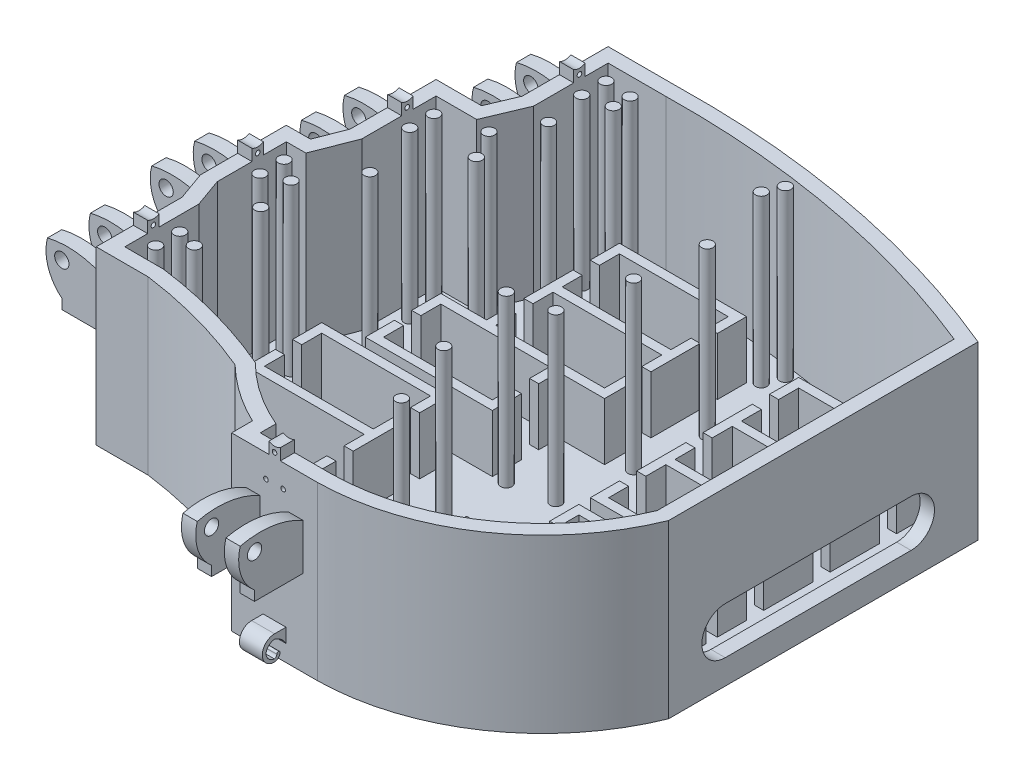
SolidWorks part; units mm, degrees
ref_plane "Front Plane" through (0, 0, 0) normal (0, 0, 1) x (1, 0, 0)
ref_plane "Top Plane" through (0, 0, 0) normal (0, 1, 0) x (1, 0, 0)
ref_plane "Right Plane" through (0, 0, 0) normal (1, 0, 0) x (0, 0, -1)
ref_plane "Palm Side Plane" through (0, 38.1, 0) normal (0, 1, 0) x (1, 0, 0)
ref_plane "Left Side Plane" through (0, 0, 63.5) normal (0, 0, 1) x (1, 0, 0)
ref_plane "Top Side Plane" through (-69.85, 0, 0) normal (1, 0, 0) x (0, 0, -1)
ref_plane "Wrist Plane" through (62.9138, 0, 0) normal (1, 0, 0) x (0, 0, -1)
sketch "Hand Direction Arrow" plane through (0, 38.1, 0) normal (0, 1, 0) x (1, 0, 0)
  line L0 (49.8191, -114.0829) -> (-36.738, -114.0829) construction
  line L1 (-36.738, -114.0829) -> (-22.4792, -131.555) construction
  line L2 (-36.738, -114.0829) -> (-22.4792, -99.8241) construction
sketch "Sketch2" plane through (0, 0, 0) normal (0, 1, 0) x (1, 0, 0)
  line L5 (-69.85, -63.5) -> (69.85, 63.5) construction
  line L6 (-69.85, 63.5) -> (69.85, -63.5) construction
  line L7 (-20.7784, 52.7587) -> (-36.189, 52.7587)
  line L8 (-36.189, 52.7587) -> (-36.189, 33.7087)
  line L9 (-42.9594, -42.4913) -> (-54.5039, -42.4913)
  line L10 (-54.5039, -42.4913) -> (-54.5039, -23.4413)
  line L11 (-54.5039, -23.4413) -> (-56.7676, -17.0913)
  line L12 (-51.4171, 1.9587) -> (-48.9477, 8.3087)
  line L14 (-56.7676, -17.0913) -> (-56.7676, 1.9587)
  line L15 (-56.7676, 1.9587) -> (-51.4171, 1.9587)
  line L16 (-38.8642, 27.3587) -> (-36.189, 33.7087)
  line L19 (15.3118, -63.2103) -> (-3.7382, -63.2103)
  line L20 (-3.7382, -63.2103) -> (-3.7382, -58.593)
  line L21 (61.5724, -31.5884) -> (61.5724, 37.0553)
  line L22 (-48.9477, 8.3087) -> (-48.9477, 27.3587)
  line L23 (-48.9477, 27.3587) -> (-38.8642, 27.3587)
  arc A0 (61.5724, 37.0553) -> (-20.7784, 52.7587) centre (-16.6219, -149.2259) ccw
  arc A2 (-42.9594, -42.4913) -> (-16.4221, -49.7553) centre (-56.8306, -145.2734) cw
  arc A5 (-3.7382, -58.593) -> (-16.4221, -49.7553) centre (16.7508, -15.6666) cw
  arc A6 (15.3118, -63.2103) -> (61.5724, -31.5884) centre (14.5642, -12.4678) ccw
  point P0 (0, 0)
  dimension "D1" = 19.05
  dimension "D2" = 19.05
  dimension "D3" = 19.05
  dimension "D4" = 19.05
  dimension "D5" = 19.05
  dimension "D6" = 6.35
  dimension "D7" = 6.35
extrude "Boss-Extrude1" add sketch "Sketch2" along normal blind 38.1
sketch "Sketch3" plane through (0, 38.1, 0) normal (0, 1, 0) x (1, 0, 0)
  line L5 (-68.58, -62.23) -> (68.58, 62.23) construction
  line L6 (-68.58, 62.23) -> (68.58, -62.23) construction
  line L7 (-20.1593, 49.595) -> (-33.014, 49.595)
  line L8 (-33.014, 49.595) -> (-33.014, 33.0672)
  line L10 (-36.189, 52.7587) -> (-36.189, 33.7087) construction
  line L11 (-54.5039, -23.4413) -> (-54.5039, -42.4913) construction
  line L12 (-42.7477, -39.3163) -> (-51.3289, -39.3163)
  line L13 (-51.3289, -39.3163) -> (-51.3289, -22.8923)
  line L18 (-53.5926, -16.5423) -> (-53.5926, -1.2163)
  line L19 (-53.5926, -1.2163) -> (-49.2452, -1.2163)
  line L22 (-56.7676, 1.9587) -> (-56.7676, -17.0913) construction
  line L23 (-51.4171, 1.9587) -> (-56.7676, 1.9587) construction
  line L24 (-45.7727, 7.713) -> (-45.7727, 24.1837)
  line L25 (-45.7727, 24.1837) -> (-36.7565, 24.1837)
  line L26 (-48.9477, 27.3587) -> (-48.9477, 8.3087) construction
  line L27 (-38.8642, 27.3587) -> (-48.9477, 27.3587) construction
  line L28 (-36.7565, 24.1837) -> (-33.014, 33.0672)
  line L29 (-36.189, 33.7087) -> (-38.8642, 27.3587) construction
  line L30 (-49.2452, -1.2163) -> (-45.7727, 7.713)
  line L31 (-54.5039, -42.4913) -> (-42.9594, -42.4913) construction
  line L32 (-51.3289, -22.8923) -> (-53.5926, -16.5423)
  line L33 (-56.7676, -17.0913) -> (-54.5039, -23.4413) construction
  line L34 (-48.9477, 8.3087) -> (-51.4171, 1.9587) construction
  line L35 (15.3312, -60.0353) -> (-0.5632, -60.0353)
  line L36 (-0.5632, -60.0353) -> (-0.5632, -56.5413)
  line L37 (-3.7382, -58.593) -> (-3.7382, -63.2103) construction
  line L38 (-3.7382, -63.2103) -> (15.3118, -63.2103) construction
  line L39 (58.3974, -30.9587) -> (58.3974, 34.9326)
  line L40 (61.5724, -31.5884) -> (61.5724, 37.0553) construction
  arc A1 (-20.1593, 49.595) -> (58.3974, 34.9326) centre (-16.6219, -149.2259) cw
  arc A4 (61.5724, 37.0553) -> (-20.7784, 52.7587) centre (-16.6219, -149.2259) ccw construction
  arc A5 (15.3118, -63.2103) -> (61.5724, -31.5884) centre (14.5642, -12.4678) ccw construction
  arc A8 (-42.7477, -39.3163) -> (-14.6223, -47.0711) centre (-56.8306, -145.2734) cw
  arc A9 (-16.4221, -49.7553) -> (-42.9594, -42.4913) centre (-56.8306, -145.2734) ccw construction
  arc A12 (15.3312, -60.0353) -> (58.3974, -30.9587) centre (14.5642, -12.4678) ccw
  arc A13 (-0.5632, -56.5413) -> (-14.6223, -47.0711) centre (16.7508, -15.6666) cw
  arc A14 (-16.4221, -49.7553) -> (-3.7382, -58.593) centre (16.7508, -15.6666) ccw construction
  point P0 (0, 0)
  point P6 (-45.5127, -25.7954)
  point P29 (-45.5127, -25.7954)
  point P52 (-54.0923, 1.9587)
  dimension "D2" = 3.175
  dimension "D3" = 3.175
  dimension "D5" = 3.175
  dimension "D6" = 3.175
  dimension "D8" = 3.175
  dimension "D4" = 3.175
  dimension "D7" = 3.175
  dimension "D9" = 3.175
  dimension "D10" = 3.175
  dimension "D11" = 3.175
  dimension "D12" = 3.175
  dimension "D13" = 3.175
  dimension "D14" = 3.175
  dimension "D15" = 3.175
  dimension "D16" = 3.175
  dimension "D17" = 3.175
extrude "Cut-Extrude1" cut sketch "Sketch3" against normal blind 36.83
sketch "Sketch6" plane through (0, 0, 0) normal (0, 1, 0) x (1, 0, 0)
  line L0 (-39.0579, -32.9145) -> (-37.0259, -32.9145)
  line L5 (-63.3937, -68.1577) -> (73.7663, 56.3023) construction
  line L6 (-64.5742, 57.9506) -> (72.5858, -66.5094) construction
  line L7 (-12.8959, -37.3595) -> (-37.0259, -37.3595)
  line L8 (-12.8959, -37.3595) -> (-12.8959, -32.9145)
  line L9 (-12.8959, -24.6595) -> (-37.0259, -24.6595)
  line L10 (-37.0259, -37.3595) -> (-37.0259, -32.9145)
  line L11 (-12.8959, -37.3595) -> (-37.0259, -24.6595) construction
  line L12 (-12.8959, -24.6595) -> (-37.0259, -37.3595) construction
  line L13 (-10.8639, -39.3915) -> (-39.0579, -39.3915)
  line L14 (-10.8639, -39.3915) -> (-10.8639, -32.9145)
  line L15 (-10.8639, -22.6275) -> (-39.0579, -22.6275)
  line L16 (-39.0579, -39.3915) -> (-39.0579, -32.9145)
  line L17 (-10.8639, -39.3915) -> (-39.0579, -22.6275) construction
  line L18 (-10.8639, -22.6275) -> (-39.0579, -39.3915) construction
  line L19 (-39.0579, -29.1045) -> (-37.0259, -29.1045)
  line L20 (-39.0579, -29.1045) -> (-39.0579, -22.6275)
  line L21 (-37.0259, -29.1045) -> (-37.0259, -24.6595)
  line L22 (-12.8959, -32.9145) -> (-10.8639, -32.9145)
  line L23 (-12.8959, -29.1045) -> (-10.8639, -29.1045)
  line L24 (-12.8959, -29.1045) -> (-12.8959, -24.6595)
  line L25 (-10.8639, -29.1045) -> (-10.8639, -22.6275)
  point P0 (5.5042, -5.6391)
  point P6 (-24.9609, -31.0095)
  point P29 (-24.9609, -31.0095)
  dimension "D6" = 2.032
  dimension "D7" = 2.032
  dimension "D9" = 12.7
  dimension "D10" = 24.13
  dimension "D11" = 4.445
  dimension "D12" = 4.445
  dimension "D13" = 4.445
  dimension "D14" = 4.445
extrude "Servo Box 1" add sketch "Sketch6" along normal blind 13.97
sketch "Sketch7" plane through (0, 0, 0) normal (0, 1, 0) x (1, 0, 0)
  line L0 (-39.0579, -18.1825) -> (-37.0259, -18.1825)
  line L5 (-10.8639, -22.6275) -> (-39.0579, -22.6275) construction
  line L6 (-39.0579, -22.6275) -> (-39.0579, -29.1045) construction
  line L7 (-12.8959, -22.6275) -> (-37.0259, -22.6275)
  line L8 (-12.8959, -22.6275) -> (-12.8959, -18.1825)
  line L9 (-12.8959, -9.9275) -> (-37.0259, -9.9275)
  line L10 (-37.0259, -22.6275) -> (-37.0259, -18.1825)
  line L11 (-12.8959, -22.6275) -> (-37.0259, -9.9275) construction
  line L12 (-12.8959, -9.9275) -> (-37.0259, -22.6275) construction
  line L13 (-10.8639, -24.6595) -> (-39.0579, -24.6595)
  line L14 (-10.8639, -24.6595) -> (-10.8639, -18.1825)
  line L15 (-10.8639, -7.8955) -> (-39.0579, -7.8955)
  line L16 (-39.0579, -24.6595) -> (-39.0579, -18.1825)
  line L17 (-10.8639, -24.6595) -> (-39.0579, -7.8955) construction
  line L18 (-10.8639, -7.8955) -> (-39.0579, -24.6595) construction
  line L19 (-39.0579, -14.3725) -> (-37.0259, -14.3725)
  line L20 (-39.0579, -14.3725) -> (-39.0579, -7.8955)
  line L21 (-37.0259, -14.3725) -> (-37.0259, -9.9275)
  line L22 (-12.8959, -18.1825) -> (-10.8639, -18.1825)
  line L23 (-12.8959, -14.3725) -> (-10.8639, -14.3725)
  line L24 (-12.8959, -14.3725) -> (-12.8959, -9.9275)
  line L25 (-10.8639, -14.3725) -> (-10.8639, -7.8955)
  point P0 (-14.8998, -5.4903)
  point P6 (-24.9609, -16.2775)
  point P29 (-24.9609, -16.2775)
  dimension "D2" = 2.032
  dimension "D3" = 0
  dimension "D6" = 2.032
  dimension "D7" = 2.032
  dimension "D9" = 12.7
  dimension "D10" = 24.13
  dimension "D11" = 4.445
  dimension "D12" = 4.445
  dimension "D13" = 4.445
  dimension "D14" = 4.445
extrude "Servo Box 2" add sketch "Sketch7" along normal blind 13.97
sketch "Sketch15" plane through (0, 0, 0) normal (0, -1, 0) x (1, 0, 0)
  line L0 (-31.4379, -4.4235) -> (-29.4059, -4.4235)
  line L5 (-10.8639, 7.8955) -> (-39.0579, 7.8955) construction
  line L6 (-39.0579, 7.8955) -> (-39.0579, 14.3725) construction
  line L7 (-5.2759, -8.8685) -> (-29.4059, -8.8685)
  line L8 (-5.2759, -8.8685) -> (-5.2759, -4.4235)
  line L9 (-5.2759, 3.8315) -> (-29.4059, 3.8315)
  line L10 (-29.4059, -8.8685) -> (-29.4059, -4.4235)
  line L11 (-5.2759, -8.8685) -> (-29.4059, 3.8315) construction
  line L12 (-5.2759, 3.8315) -> (-29.4059, -8.8685) construction
  line L13 (-3.2439, -10.9005) -> (-31.4379, -10.9005)
  line L14 (-3.2439, -10.9005) -> (-3.2439, -4.4235)
  line L15 (-3.2439, 5.8635) -> (-31.4379, 5.8635)
  line L16 (-31.4379, -10.9005) -> (-31.4379, -4.4235)
  line L17 (-3.2439, -10.9005) -> (-31.4379, 5.8635) construction
  line L18 (-3.2439, 5.8635) -> (-31.4379, -10.9005) construction
  line L19 (-31.4379, -0.6135) -> (-29.4059, -0.6135)
  line L20 (-31.4379, -0.6135) -> (-31.4379, 5.8635)
  line L21 (-29.4059, -0.6135) -> (-29.4059, 3.8315)
  line L22 (-5.2759, -4.4235) -> (-3.2439, -4.4235)
  line L23 (-5.2759, -0.6135) -> (-3.2439, -0.6135)
  line L24 (-5.2759, -0.6135) -> (-5.2759, 3.8315)
  line L25 (-3.2439, -0.6135) -> (-3.2439, 5.8635)
  point P0 (-6.5637, 8.998)
  point P6 (-17.3409, -2.5185)
  point P29 (-17.3409, -2.5185)
  dimension "D2" = 2.032
  dimension "D3" = 7.62
  dimension "D6" = 2.032
  dimension "D7" = 2.032
  dimension "D9" = 12.7
  dimension "D10" = 24.13
  dimension "D11" = 4.445
  dimension "D12" = 4.445
  dimension "D13" = 4.445
  dimension "D14" = 4.445
extrude "Servo Box 3" add sketch "Sketch15" against normal blind 13.97
sketch "Sketch16" plane through (0, 0, 0) normal (0, -1, 0) x (1, 0, 0)
  line L0 (-21.2779, -19.1555) -> (-19.2459, -19.1555)
  line L5 (-31.4379, -10.9005) -> (-3.2439, -10.9005) construction
  line L6 (-31.4379, -4.4235) -> (-31.4379, -10.9005) construction
  line L7 (4.8841, -23.6005) -> (-19.2459, -23.6005)
  line L8 (4.8841, -23.6005) -> (4.8841, -19.1555)
  line L9 (4.8841, -10.9005) -> (-19.2459, -10.9005)
  line L10 (-19.2459, -23.6005) -> (-19.2459, -19.1555)
  line L11 (4.8841, -23.6005) -> (-19.2459, -10.9005) construction
  line L12 (4.8841, -10.9005) -> (-19.2459, -23.6005) construction
  line L13 (6.9161, -25.6325) -> (-21.2779, -25.6325)
  line L14 (6.9161, -25.6325) -> (6.9161, -19.1555)
  line L15 (6.9161, -8.8685) -> (-21.2779, -8.8685)
  line L16 (-21.2779, -25.6325) -> (-21.2779, -19.1555)
  line L17 (6.9161, -25.6325) -> (-21.2779, -8.8685) construction
  line L18 (6.9161, -8.8685) -> (-21.2779, -25.6325) construction
  line L19 (-21.2779, -15.3455) -> (-19.2459, -15.3455)
  line L20 (-21.2779, -15.3455) -> (-21.2779, -8.8685)
  line L21 (-19.2459, -15.3455) -> (-19.2459, -10.9005)
  line L22 (4.8841, -19.1555) -> (6.9161, -19.1555)
  line L23 (4.8841, -15.3455) -> (6.9161, -15.3455)
  line L24 (4.8841, -15.3455) -> (4.8841, -10.9005)
  line L25 (6.9161, -15.3455) -> (6.9161, -8.8685)
  point P0 (1.9027, -6.9539)
  point P6 (-7.1809, -17.2505)
  point P29 (-7.1809, -17.2505)
  dimension "D2" = 2.032
  dimension "D3" = 10.16
  dimension "D6" = 2.032
  dimension "D7" = 2.032
  dimension "D9" = 12.7
  dimension "D10" = 24.13
  dimension "D11" = 4.445
  dimension "D12" = 4.445
  dimension "D13" = 4.445
  dimension "D14" = 4.445
extrude "Servo Box 4" add sketch "Sketch16" against normal blind 13.97
sketch "Sketch17" plane through (0, 0, 0) normal (0, -1, 0) x (1, 0, 0)
  line L0 (-21.2779, -33.8875) -> (-19.2459, -33.8875)
  line L5 (-21.2779, -25.6325) -> (6.9161, -25.6325) construction
  line L6 (-21.2779, -19.1555) -> (-21.2779, -25.6325) construction
  line L7 (4.8841, -38.3325) -> (-19.2459, -38.3325)
  line L8 (4.8841, -38.3325) -> (4.8841, -33.8875)
  line L9 (4.8841, -25.6325) -> (-19.2459, -25.6325)
  line L10 (-19.2459, -38.3325) -> (-19.2459, -33.8875)
  line L11 (4.8841, -38.3325) -> (-19.2459, -25.6325) construction
  line L12 (4.8841, -25.6325) -> (-19.2459, -38.3325) construction
  line L13 (6.9161, -40.3645) -> (-21.2779, -40.3645)
  line L14 (6.9161, -40.3645) -> (6.9161, -33.8875)
  line L15 (6.9161, -23.6005) -> (-21.2779, -23.6005)
  line L16 (-21.2779, -40.3645) -> (-21.2779, -33.8875)
  line L17 (6.9161, -40.3645) -> (-21.2779, -23.6005) construction
  line L18 (6.9161, -23.6005) -> (-21.2779, -40.3645) construction
  line L19 (-21.2779, -30.0775) -> (-19.2459, -30.0775)
  line L20 (-21.2779, -30.0775) -> (-21.2779, -23.6005)
  line L21 (-19.2459, -30.0775) -> (-19.2459, -25.6325)
  line L22 (4.8841, -33.8875) -> (6.9161, -33.8875)
  line L23 (4.8841, -30.0775) -> (6.9161, -30.0775)
  line L24 (4.8841, -30.0775) -> (4.8841, -25.6325)
  line L25 (6.9161, -30.0775) -> (6.9161, -23.6005)
  point P0 (6.1079, -24.4951)
  point P6 (-7.1809, -31.9825)
  point P10 (-24.8195, -22.5077)
  point P29 (-7.1809, -31.9825)
  dimension "D2" = 2.032
  dimension "D3" = 0
  dimension "D6" = 2.032
  dimension "D7" = 2.032
  dimension "D9" = 12.7
  dimension "D10" = 24.13
  dimension "D11" = 4.445
  dimension "D12" = 4.445
  dimension "D13" = 4.445
  dimension "D14" = 4.445
extrude "Servo Box 5" add sketch "Sketch17" against normal blind 13.97
sketch "Sketch18" plane through (0, 0, 0) normal (0, -1, 0) x (1, 0, 0)
  line L0 (14.219, 35.5105) -> (16.251, 35.5105)
  line L7 (40.381, 31.0655) -> (16.251, 31.0655)
  line L8 (40.381, 31.0655) -> (40.381, 35.5105)
  line L9 (40.381, 43.7655) -> (16.251, 43.7655)
  line L10 (16.251, 31.0655) -> (16.251, 35.5105)
  line L11 (40.381, 31.0655) -> (16.251, 43.7655) construction
  line L12 (40.381, 43.7655) -> (16.251, 31.0655) construction
  line L13 (42.413, 29.0335) -> (14.219, 29.0335)
  line L14 (42.413, 29.0335) -> (42.413, 35.5105)
  line L15 (42.413, 45.7975) -> (14.219, 45.7975)
  line L16 (14.219, 29.0335) -> (14.219, 35.5105)
  line L17 (42.413, 29.0335) -> (14.219, 45.7975) construction
  line L18 (42.413, 45.7975) -> (14.219, 29.0335) construction
  line L19 (14.219, 39.3205) -> (16.251, 39.3205)
  line L20 (14.219, 39.3205) -> (14.219, 45.7975)
  line L21 (16.251, 39.3205) -> (16.251, 43.7655)
  line L22 (40.381, 35.5105) -> (42.413, 35.5105)
  line L23 (40.381, 39.3205) -> (42.413, 39.3205)
  line L24 (40.381, 39.3205) -> (40.381, 43.7655)
  line L25 (42.413, 39.3205) -> (42.413, 45.7975)
  point P0 (43.5107, 47.2957)
  point P6 (28.316, 37.4155)
  point P29 (28.316, 37.4155)
  dimension "D6" = 2.032
  dimension "D7" = 2.032
  dimension "D9" = 12.7
  dimension "D10" = 24.13
  dimension "D11" = 4.445
  dimension "D12" = 4.445
  dimension "D13" = 4.445
  dimension "D14" = 4.445
extrude "Servo Box 6" add sketch "Sketch18" against normal blind 13.97
sketch "Sketch19" plane through (0, 0, 0) normal (0, -1, 0) x (1, 0, 0)
  line L0 (24.379, 20.7785) -> (26.411, 20.7785)
  line L5 (14.219, 29.0335) -> (42.413, 29.0335) construction
  line L6 (14.219, 35.5105) -> (14.219, 29.0335) construction
  line L7 (50.541, 16.3335) -> (26.411, 16.3335)
  line L8 (50.541, 16.3335) -> (50.541, 20.7785)
  line L9 (50.541, 29.0335) -> (26.411, 29.0335)
  line L10 (26.411, 16.3335) -> (26.411, 20.7785)
  line L11 (50.541, 16.3335) -> (26.411, 29.0335) construction
  line L12 (50.541, 29.0335) -> (26.411, 16.3335) construction
  line L13 (52.573, 14.3015) -> (24.379, 14.3015)
  line L14 (52.573, 14.3015) -> (52.573, 20.7785)
  line L15 (52.573, 31.0655) -> (24.379, 31.0655)
  line L16 (24.379, 14.3015) -> (24.379, 20.7785)
  line L17 (52.573, 14.3015) -> (24.379, 31.0655) construction
  line L18 (52.573, 31.0655) -> (24.379, 14.3015) construction
  line L19 (24.379, 24.5885) -> (26.411, 24.5885)
  line L20 (24.379, 24.5885) -> (24.379, 31.0655)
  line L21 (26.411, 24.5885) -> (26.411, 29.0335)
  line L22 (50.541, 20.7785) -> (52.573, 20.7785)
  line L23 (50.541, 24.5885) -> (52.573, 24.5885)
  line L24 (50.541, 24.5885) -> (50.541, 29.0335)
  line L25 (52.573, 24.5885) -> (52.573, 31.0655)
  point P0 (52.4146, 37.8023)
  point P6 (38.476, 22.6835)
  point P29 (38.476, 22.6835)
  dimension "D2" = 2.032
  dimension "D3" = 10.16
  dimension "D6" = 2.032
  dimension "D7" = 2.032
  dimension "D9" = 12.7
  dimension "D10" = 24.13
  dimension "D11" = 4.445
  dimension "D12" = 4.445
  dimension "D13" = 4.445
  dimension "D14" = 4.445
extrude "Servo Box 7" add sketch "Sketch19" against normal blind 13.97
sketch "Sketch20" plane through (0, 0, 0) normal (0, -1, 0) x (1, 0, 0)
  line L0 (24.379, 1.4745) -> (26.411, 1.4745)
  line L5 (24.379, 20.7785) -> (24.379, 14.3015) construction
  line L6 (24.379, 14.3015) -> (52.573, 14.3015) construction
  line L7 (50.541, -2.9705) -> (26.411, -2.9705)
  line L8 (50.541, -2.9705) -> (50.541, 1.4745)
  line L9 (50.541, 9.7295) -> (26.411, 9.7295)
  line L10 (26.411, -2.9705) -> (26.411, 1.4745)
  line L11 (50.541, -2.9705) -> (26.411, 9.7295) construction
  line L12 (50.541, 9.7295) -> (26.411, -2.9705) construction
  line L13 (52.573, -5.0025) -> (24.379, -5.0025)
  line L14 (52.573, -5.0025) -> (52.573, 1.4745)
  line L15 (52.573, 11.7615) -> (24.379, 11.7615)
  line L16 (24.379, -5.0025) -> (24.379, 1.4745)
  line L17 (52.573, -5.0025) -> (24.379, 11.7615) construction
  line L18 (52.573, 11.7615) -> (24.379, -5.0025) construction
  line L19 (24.379, 5.2845) -> (26.411, 5.2845)
  line L20 (24.379, 5.2845) -> (24.379, 11.7615)
  line L21 (26.411, 5.2845) -> (26.411, 9.7295)
  line L22 (50.541, 1.4745) -> (52.573, 1.4745)
  line L23 (50.541, 5.2845) -> (52.573, 5.2845)
  line L24 (50.541, 5.2845) -> (50.541, 9.7295)
  line L25 (52.573, 5.2845) -> (52.573, 11.7615)
  point P0 (54.8865, 20.8211)
  point P6 (38.476, 3.3795)
  point P29 (38.476, 3.3795)
  dimension "D2" = 0
  dimension "D3" = 2.54
  dimension "D6" = 2.032
  dimension "D7" = 2.032
  dimension "D9" = 12.7
  dimension "D10" = 24.13
  dimension "D11" = 4.445
  dimension "D12" = 4.445
  dimension "D13" = 4.445
  dimension "D14" = 4.445
extrude "Servo Box 8" add sketch "Sketch20" against normal blind 13.97
sketch "Sketch21" plane through (0, 0, 0) normal (0, -1, 0) x (1, 0, 0)
  line L0 (24.379, -13.2575) -> (26.411, -13.2575)
  line L5 (24.379, -5.0025) -> (52.573, -5.0025) construction
  line L6 (24.379, 1.4745) -> (24.379, -5.0025) construction
  line L7 (50.541, -17.7025) -> (26.411, -17.7025)
  line L8 (50.541, -17.7025) -> (50.541, -13.2575)
  line L9 (50.541, -5.0025) -> (26.411, -5.0025)
  line L10 (26.411, -17.7025) -> (26.411, -13.2575)
  line L11 (50.541, -17.7025) -> (26.411, -5.0025) construction
  line L12 (50.541, -5.0025) -> (26.411, -17.7025) construction
  line L13 (52.573, -19.7345) -> (24.379, -19.7345)
  line L14 (52.573, -19.7345) -> (52.573, -13.2575)
  line L15 (52.573, -2.9705) -> (24.379, -2.9705)
  line L16 (24.379, -19.7345) -> (24.379, -13.2575)
  line L17 (52.573, -19.7345) -> (24.379, -2.9705) construction
  line L18 (52.573, -2.9705) -> (24.379, -19.7345) construction
  line L19 (24.379, -9.4475) -> (26.411, -9.4475)
  line L20 (24.379, -9.4475) -> (24.379, -2.9705)
  line L21 (26.411, -9.4475) -> (26.411, -5.0025)
  line L22 (50.541, -13.2575) -> (52.573, -13.2575)
  line L23 (50.541, -9.4475) -> (52.573, -9.4475)
  line L24 (50.541, -9.4475) -> (50.541, -5.0025)
  line L25 (52.573, -9.4475) -> (52.573, -2.9705)
  point P0 (52.1156, 3.8173)
  point P6 (38.476, -11.3525)
  point P29 (38.476, -11.3525)
  dimension "D2" = 2.032
  dimension "D3" = 0
  dimension "D6" = 2.032
  dimension "D7" = 2.032
  dimension "D9" = 12.7
  dimension "D10" = 24.13
  dimension "D11" = 4.445
  dimension "D12" = 4.445
  dimension "D13" = 4.445
  dimension "D14" = 4.445
extrude "Servo Box 9" add sketch "Sketch21" against normal blind 13.97
sketch "Sketch22" plane through (0, 0, 0) normal (0, -1, 0) x (1, 0, 0)
  line L0 (24.379, -27.9895) -> (26.411, -27.9895)
  line L5 (24.379, -19.7345) -> (52.573, -19.7345) construction
  line L6 (24.379, -13.2575) -> (24.379, -19.7345) construction
  line L7 (50.541, -32.4345) -> (26.411, -32.4345)
  line L8 (50.541, -32.4345) -> (50.541, -27.9895)
  line L9 (50.541, -19.7345) -> (26.411, -19.7345)
  line L10 (26.411, -32.4345) -> (26.411, -27.9895)
  line L11 (50.541, -32.4345) -> (26.411, -19.7345) construction
  line L12 (50.541, -19.7345) -> (26.411, -32.4345) construction
  line L13 (52.573, -34.4665) -> (24.379, -34.4665)
  line L14 (52.573, -34.4665) -> (52.573, -27.9895)
  line L15 (52.573, -17.7025) -> (24.379, -17.7025)
  line L16 (24.379, -34.4665) -> (24.379, -27.9895)
  line L17 (52.573, -34.4665) -> (24.379, -17.7025) construction
  line L18 (52.573, -17.7025) -> (24.379, -34.4665) construction
  line L19 (24.379, -24.1795) -> (26.411, -24.1795)
  line L20 (24.379, -24.1795) -> (24.379, -17.7025)
  line L21 (26.411, -24.1795) -> (26.411, -19.7345)
  line L22 (50.541, -27.9895) -> (52.573, -27.9895)
  line L23 (50.541, -24.1795) -> (52.573, -24.1795)
  line L24 (50.541, -24.1795) -> (50.541, -19.7345)
  line L25 (52.573, -24.1795) -> (52.573, -17.7025)
  point P0 (57.6091, -14.277)
  point P6 (38.476, -26.0845)
  point P29 (38.476, -26.0845)
  dimension "D3" = 0
  dimension "D6" = 2.032
  dimension "D7" = 2.032
  dimension "D9" = 12.7
  dimension "D10" = 24.13
  dimension "D11" = 4.445
  dimension "D12" = 4.445
  dimension "D13" = 4.445
  dimension "D14" = 4.445
  dimension "0" = 2.032
extrude "Servo Box 10" add sketch "Sketch22" against normal blind 13.97
sketch "Sketch25" plane through (0, 0, 63.5) normal (0, 0, 1) x (1, 0, 0)
  line L0 (15.3118, 38.1) -> (15.3118, 0) construction
  line L1 (49.8191, 38.1) -> (-36.738, 38.1) construction
  line L6 (-3.7382, 38.1) -> (-3.7382, 0) construction
  circle A0 centre (7.6918, 33.02) radius 0.508
  circle A1 centre (3.8818, 33.02) radius 0.508
  dimension "D3" = 7.62
  dimension "D1" = 5.08
  dimension "D2" = 5.08
  dimension "D4" = 7.62
extrude "Thumb Holes" cut sketch "Sketch25" against normal blind 12.7
sketch "Sketch31" plane through (-69.85, 0, 0) normal (1, 0, 0) x (0, 0, -1)
  line L0 (-23.4413, 38.1) -> (-23.4413, 0) construction
  line L1 (-23.4413, 38.1) -> (-42.4913, 38.1) construction
  line L2 (-42.4913, 38.1) -> (-42.4913, 0) construction
  circle A0 centre (-31.0613, 33.02) radius 0.508
  circle A1 centre (-34.8713, 33.02) radius 0.508
  dimension "D1" = 7.62
  dimension "D2" = 5.08
  dimension "D3" = 5.08
  dimension "D4" = 7.62
extrude "Index Finger Holes" cut sketch "Sketch31" along normal blind 17.018
sketch "Sketch32" plane through (-69.85, 0, 0) normal (1, 0, 0) x (0, 0, -1)
  line L0 (1.9587, 38.1) -> (1.9587, 0) construction
  line L1 (-17.0913, 38.1) -> (-17.0913, 0) construction
  line L2 (1.9587, 38.1) -> (-17.0913, 38.1) construction
  circle A0 centre (-9.4713, 33.02) radius 0.508
  circle A1 centre (-5.6613, 33.02) radius 0.508
  dimension "D1" = 7.62
  dimension "D2" = 7.62
  dimension "D3" = 5.08
  dimension "D4" = 5.08
extrude "Middle Finger Holes" cut sketch "Sketch32" along normal blind 15.24
sketch "Sketch33" plane through (-69.85, 0, 0) normal (1, 0, 0) x (0, 0, -1)
  line L0 (27.3587, 38.1) -> (27.3587, 0) construction
  line L1 (27.3587, 38.1) -> (8.3087, 38.1) construction
  line L2 (8.3087, 38.1) -> (8.3087, 0) construction
  circle A0 centre (15.9287, 33.02) radius 0.508
  circle A1 centre (19.7387, 33.02) radius 0.508
  dimension "D1" = 7.62
  dimension "D2" = 5.08
  dimension "D3" = 5.08
  dimension "D4" = 7.62
extrude "Ring Finger Holes" cut sketch "Sketch33" along normal blind 22.86
sketch "Sketch34" plane through (-69.85, 0, 0) normal (1, 0, 0) x (0, 0, -1)
  line L0 (52.7587, 38.1) -> (33.7087, 38.1) construction
  line L1 (52.8014, 0) -> (52.8014, 38.1) construction
  line L2 (33.7087, 38.1) -> (33.7087, 0) construction
  circle A0 centre (41.3287, 33.02) radius 0.508
  circle A1 centre (45.1814, 33.02) radius 0.508
  dimension "D1" = 5.08
  dimension "D2" = 7.62
  dimension "D3" = 7.62
  dimension "D4" = 5.08
extrude "Pinky Finger Holes" cut sketch "Sketch34" along normal blind 35.56
sketch "Sketch26" plane through (0, 38.1, 0) normal (0, 1, 0) x (1, 0, 0)
  line L0 (-0.402, -6.8775) -> (-45.6139, -6.8775) construction
  line L1 (11.5354, 25.767) -> (11.5354, 45.6179) construction
  line L2 (9.9312, 11.035) -> (9.9312, 41.8857) construction
  line L3 (-25.4393, 41.8857) -> (-25.4393, 45.6179) construction
  line L4 (-51.3289, -22.8923) -> (-51.3289, -39.3163) construction
  line L5 (-37.0259, -18.1825) -> (-39.0579, -18.1825) construction
  line L6 (14.219, -39.3205) -> (16.251, -39.3205) construction
  line L7 (24.379, -24.5885) -> (26.411, -24.5885) construction
  line L8 (24.379, -5.2845) -> (26.411, -5.2845) construction
  line L9 (24.379, 9.4475) -> (26.411, 9.4475) construction
  line L10 (24.379, 24.1795) -> (26.411, 24.1795) construction
  line L11 (-31.4379, 0.6135) -> (-29.4059, 0.6135) construction
  line L12 (-21.2779, 15.3455) -> (-19.2459, 15.3455) construction
  line L13 (-21.2779, 30.0775) -> (-19.2459, 30.0775) construction
  line L14 (8.6612, 43.1557) -> (-24.1693, 43.1557) construction
  line L15 (10.2654, 46.8879) -> (-24.1693, 46.8879) construction
  line L16 (-51.3289, -22.8923) -> (-51.3289, -39.3163) construction
  line L17 (-53.5926, -1.2163) -> (-53.5926, -16.5423) construction
  line L18 (-45.7727, 24.1837) -> (-45.7727, 7.713) construction
  line L19 (-45.7727, 24.1837) -> (-45.7727, 7.713) construction
  line L20 (-33.014, 49.595) -> (-33.014, 33.0672) construction
  line L21 (-33.014, 49.595) -> (-33.014, 33.0672) construction
  line L22 (-37.0259, -32.9145) -> (-39.0579, -32.9145) construction
  line L23 (-46.8839, -8.1475) -> (-46.8839, -35.6333) construction
  circle A0 centre (8.4538, -37.733) radius 1.27
  circle A1 centre (3.1198, -23.001) radius 1.27
  circle A2 centre (8.6784, -3.697) radius 1.27
  circle A3 centre (11.2012, 11.035) radius 1.27
  circle A4 centre (12.8054, 25.767) radius 1.27
  circle A5 centre (-0.402, -5.6075) radius 1.27
  circle A6 centre (10.2654, 45.6179) radius 1.27
  circle A7 centre (8.6612, 41.8857) radius 1.27
  circle A8 centre (-45.6139, -8.1475) radius 1.27
  circle A9 centre (-50.4176, -10.2333) radius 1.27
  circle A10 centre (-50.4176, -4.8993) radius 1.27
  circle A11 centre (-43.8931, -16.595) radius 1.27
  circle A12 centre (-38.4803, 2.201) radius 1.27
  circle A13 centre (-29.6038, 16.933) radius 1.27
  circle A14 centre (-42.5977, 15.1667) radius 1.27
  circle A15 centre (-28.3016, 31.665) radius 1.27
  circle A16 centre (-33.047, 23.1942) radius 1.27
  circle A17 centre (-42.5977, 20.5007) radius 1.27
  circle A18 centre (-24.1693, 41.8857) radius 1.27
  circle A19 centre (-24.1693, 45.6179) radius 1.27
  circle A20 centre (-29.839, 40.5667) radius 1.27
  circle A21 centre (-29.839, 45.9434) radius 1.27
  circle A22 centre (-48.1539, -35.6333) radius 1.27
  circle A23 centre (-48.1539, -30.2993) radius 1.27
  circle A24 centre (-43.8931, -31.327) radius 1.27
  dimension "D6" = 0.254
  dimension "D7" = 0.254
  dimension "D14" = 2.54
  dimension "D15" = 2.54
  dimension "D16" = 2.54
  dimension "D17" = 2.54
  dimension "D18" = 2.54
  dimension "D19" = 2.54
  dimension "D20" = 2.54
  dimension "D21" = 2.54
  dimension "D22" = 2.54
  dimension "D23" = 2.54
  dimension "D24" = 2.54
  dimension "D25" = 2.54
  dimension "D26" = 2.54
  dimension "D27" = 2.54
  dimension "D28" = 2.54
  dimension "D29" = 2.54
  dimension "D30" = 2.54
  dimension "D31" = 2.54
  dimension "D32" = 2.54
  dimension "D33" = 2.54
  dimension "D34" = 2.54
  dimension "D35" = 2.54
  dimension "D41" = 0.254
  dimension "D52" = 2.54
  dimension "D42" = 2.54
  dimension "D53" = 2.54
  dimension "D1" = 1.5875
  dimension "D2" = 1.5875
  dimension "D3" = 1.5875
  dimension "D4" = 1.5875
  dimension "D5" = 1.5875
  dimension "D8" = 1.5875
  dimension "D9" = 1.5875
  dimension "D10" = 1.5875
  dimension "D11" = 1.5875
  dimension "D12" = 0.254
  dimension "D13" = 0.254
  dimension "D36" = 0.254
  dimension "D37" = 0.254
  dimension "D38" = 0.254
  dimension "D39" = 0.254
  dimension "D40" = 0.254
  dimension "D43" = 3.175
  dimension "D44" = 3.175
  dimension "D45" = 3.175
  dimension "D46" = 3.175
  dimension "D47" = 3.175
  dimension "D48" = 3.175
  dimension "D49" = 3.175
  dimension "D50" = 3.175
  dimension "D51" = 1.5875
extrude "Guide Poles" add sketch "Sketch26" against normal blind 36.83
ref_plane "Pinky Attachment Plane" through (0, 0, -52.7587) normal (0, 0, -1) x (-1, 0, 0)
ref_plane "Ring Attachment Plane" through (0, 0, -27.3587) normal (0, 0, -1) x (-1, 0, 0)
ref_plane "Middle Attachment Plane" through (0, 0, -1.9587) normal (0, 0, -1) x (-1, 0, 0)
ref_plane "Pointer Attachment Plane" through (0, 0, 23.4413) normal (0, 0, -1) x (-1, 0, 0)
ref_plane "Thumb Attachment Plane" through (-3.7382, 0, 0) normal (-1, 0, 0) x (0, 0, 1)
sketch "Sketch35" plane through (0, 0, -52.7587) normal (0, 0, -1) x (-1, 0, 0)
  line L1 (36.189, 38.1) -> (36.189, 0) construction
  line L2 (38.8642, 38.1) -> (48.9477, 38.1) construction
  line L3 (36.189, 19.05) -> (40.634, 19.05)
  line L4 (40.634, 38.1) -> (40.634, 19.05) construction
  line L5 (36.189, 29.21) -> (36.189, 19.05)
  line L6 (36.189, 38.1) -> (36.189, 0) construction
  line L7 (40.634, 19.05) -> (46.984, 19.05)
  line L9 (46.984, 19.05) -> (46.984, 21.2492)
  circle A1 centre (46.984, 28.575) radius 1.5875
  arc A2 (50.159, 31.242) -> (46.984, 21.2492) centre (40.8478, 28.6996) cw
  arc A3 (50.159, 31.242) -> (36.189, 29.21) centre (45.7208, 12.7162) ccw
  dimension "D1" = 10.795
  dimension "D2" = 4.445
  dimension "D3" = 8.89
  dimension "D6" = 10.795
  dimension "D4" = 6.858
  dimension "D5" = 13.97
extrude "Pinky Attachment" add sketch "Sketch35" against normal blind 19.05
sketch "Sketch36" plane through (0, 0, -27.3587) normal (0, 0, -1) x (-1, 0, 0)
  line L0 (51.4171, 38.1) -> (56.7676, 38.1) construction
  line L3 (48.9477, 29.21) -> (48.9477, 19.05)
  line L4 (48.9477, 38.1) -> (48.9477, 0) construction
  line L5 (48.9477, 19.05) -> (53.3927, 19.05)
  line L6 (53.3927, 38.1) -> (53.3927, 19.05) construction
  line L7 (48.9477, 38.1) -> (48.9477, 0) construction
  line L8 (53.3927, 19.05) -> (59.7427, 19.05)
  line L9 (59.7427, 19.05) -> (59.7427, 21.2492)
  arc A0 (62.9177, 31.242) -> (59.7427, 21.2492) centre (53.6065, 28.6996) cw
  circle A1 centre (59.7427, 28.7074) radius 1.5875
  arc A2 (48.9477, 29.21) -> (62.9177, 31.242) centre (58.4796, 12.7162) cw
  dimension "D1" = 4.445
  dimension "D2" = 10.795
  dimension "D3" = 13.97
  dimension "D5" = 10.795
  dimension "D4" = 6.858
extrude "Ring Attachment" add sketch "Sketch36" against normal blind 19.05
sketch "Sketch37" plane through (0, 0, -1.9587) normal (0, 0, -1) x (-1, 0, 0)
  line L0 (51.4171, 38.1) -> (56.7676, 38.1) construction
  line L2 (56.7676, 29.21) -> (56.7676, 19.05)
  line L3 (56.7676, 38.1) -> (56.7676, 0) construction
  line L4 (56.7676, 19.05) -> (61.2126, 19.05)
  line L7 (61.2126, 38.1) -> (61.2126, 19.05) construction
  line L8 (61.2126, 19.05) -> (67.5626, 19.05)
  line L9 (67.5626, 19.05) -> (67.5626, 21.2492)
  arc A2 (70.7376, 31.242) -> (67.5626, 21.2492) centre (61.4264, 28.6996) cw
  circle A3 centre (67.5626, 28.575) radius 1.5875
  arc A4 (56.7676, 29.21) -> (70.7376, 31.242) centre (66.2994, 12.7162) cw
  dimension "D1" = 4.445
  dimension "D4" = 10.795
  dimension "D3" = 13.97
  dimension "D2" = 10.795
  dimension "D5" = 6.858
extrude "Middle Attachment" add sketch "Sketch37" against normal blind 19.05
sketch "Sketch38" plane through (0, 0, 23.4413) normal (0, 0, -1) x (-1, 0, 0)
  line L0 (51.4171, 38.1) -> (56.7676, 38.1) construction
  line L3 (58.9489, 38.1) -> (58.9489, 19.05) construction
  line L5 (54.5039, 38.1) -> (54.5039, 0) construction
  line L6 (54.5039, 38.1) -> (54.5039, 0) construction
  line L7 (54.5039, 29.21) -> (54.5039, 19.05)
  line L9 (56.7676, 19.05) -> (67.5626, 19.05) construction
  line L10 (65.2989, 19.05) -> (65.2989, 21.2492)
  line L11 (65.2989, 19.05) -> (54.5039, 19.05)
  arc A2 (68.4739, 31.242) -> (65.2989, 21.2492) centre (59.1628, 28.6996) cw
  circle A3 centre (65.2989, 28.575) radius 1.5875
  arc A4 (54.5039, 29.21) -> (68.4739, 31.242) centre (64.0358, 12.7162) cw
  dimension "D3" = 13.97
  dimension "D1" = 4.445
  dimension "D5" = 10.795
  dimension "D2" = 10.795
  dimension "D4" = 6.858
extrude "Pointer Attachment" add sketch "Sketch38" against normal blind 19.05
sketch "Sketch39" plane through (-3.7382, 0, 0) normal (-1, 0, 0) x (0, 0, 1)
  line L0 (63.2103, 38.1) -> (63.2103, 0) construction
  line L4 (63.2103, 19.05) -> (67.6553, 19.05)
  line L6 (63.2103, 29.21) -> (63.2103, 19.05)
  line L7 (67.6553, 38.1) -> (67.6553, 19.05) construction
  line L8 (67.6553, 19.05) -> (74.0053, 19.05)
  line L9 (74.0053, 19.05) -> (74.0053, 21.2492)
  arc A0 (77.1803, 31.242) -> (74.0053, 21.2492) centre (67.8692, 28.6996) cw
  circle A1 centre (74.0053, 28.575) radius 1.5875
  arc A2 (63.2103, 29.21) -> (77.1803, 31.242) centre (72.7422, 12.7162) cw
  dimension "D1" = 4.445
  dimension "D3" = 13.97
  dimension "D5" = 10.795
  dimension "D2" = 10.795
  dimension "D4" = 6.858
extrude "Thumb Attachment" add sketch "Sketch39" against normal blind 19.05
sketch "Sketch40" plane through (0, 38.1, 0) normal (0, 1, 0) x (1, 0, 0)
  line L0 (-56.7676, 1.9587) -> (-56.7676, -17.0913) construction
  line L1 (2.6118, -63.2103) -> (8.9618, -63.2103)
  line L2 (2.6118, -63.2103) -> (2.6118, -80.1392)
  line L4 (8.9618, -63.2103) -> (8.9618, -80.1964)
  line L5 (-0.5632, -63.2103) -> (-0.5632, -80.1392)
  line L6 (-0.5632, -80.1392) -> (2.6118, -80.1392)
  line L7 (-6.4204, -63.2103) -> (-0.5632, -63.2103)
  line L8 (15.3118, -63.2103) -> (12.1368, -63.2103)
  line L9 (12.1368, -63.2103) -> (12.1368, -80.1964)
  line L10 (12.1368, -80.1964) -> (8.9618, -80.1964)
  line L11 (-54.5039, -42.4913) -> (-54.5039, -39.3163)
  line L13 (-54.5039, -39.3163) -> (-69.4507, -39.3163)
  line L15 (-69.4507, -39.3163) -> (-69.4507, -36.1413)
  line L16 (-69.4507, -36.1413) -> (-54.5039, -36.1413)
  line L17 (-54.5039, -36.1413) -> (-54.5039, -29.7913)
  line L18 (-54.5039, -29.7913) -> (-69.5228, -29.7913)
  line L19 (-69.5228, -29.7913) -> (-69.5228, -26.6163)
  line L20 (-69.5228, -26.6163) -> (-54.5039, -26.6163)
  line L21 (-54.5039, -26.6163) -> (-54.5039, -23.4413)
  line L22 (-56.7676, -17.0913) -> (-56.7676, -13.9163)
  line L24 (-56.7676, -13.9163) -> (-71.425, -13.9163)
  line L25 (-71.425, -13.9163) -> (-71.425, -10.7413)
  line L26 (-71.425, -10.7413) -> (-56.7676, -10.7413)
  line L27 (-56.7676, -10.7413) -> (-56.7676, -4.3913)
  line L28 (-56.7676, -4.3913) -> (-71.3004, -4.3913)
  line L29 (-71.3004, -4.3913) -> (-71.3004, -1.2163)
  line L31 (-56.7676, -1.2163) -> (-56.7676, 1.9587)
  line L32 (-71.3004, -1.2163) -> (-56.7676, -1.2163)
  line L33 (-45.7727, 24.1837) -> (-45.7727, 7.713) construction
  line L34 (-48.9477, 8.3087) -> (-48.9477, 11.4837)
  line L36 (-48.9477, 11.4837) -> (-65.3617, 11.4837)
  line L37 (-65.3617, 11.4837) -> (-65.3617, 14.6587)
  line L38 (-65.3617, 14.6587) -> (-48.9477, 14.6587)
  line L39 (-48.9477, 14.6587) -> (-48.9477, 21.0087)
  line L40 (-48.9477, 21.0087) -> (-65.7763, 21.0087)
  line L41 (-65.7763, 21.0087) -> (-65.7763, 24.1837)
  line L42 (-65.7763, 24.1837) -> (-48.9477, 24.1837)
  line L43 (-48.9477, 24.1837) -> (-48.9477, 27.3587)
  line L44 (-36.189, 33.7087) -> (-36.189, 36.8837)
  line L45 (-0.5632, -60.0353) -> (15.3312, -60.0353) construction
  line L46 (-36.189, 36.8837) -> (-51.8787, 36.8837)
  line L47 (-51.8787, 36.8837) -> (-51.8787, 40.0587)
  line L48 (-51.8787, 40.0587) -> (-36.189, 40.0587)
  line L49 (-36.189, 40.0587) -> (-36.189, 46.4087)
  line L50 (-36.189, 46.4087) -> (-51.7392, 46.4087)
  line L51 (-51.7392, 46.4087) -> (-51.7392, 49.5837)
  line L52 (-51.7392, 49.5837) -> (-36.189, 49.5837)
  line L53 (-36.189, 49.5837) -> (-36.189, 52.7587)
  line L54 (15.3118, -63.2103) -> (-3.7382, -63.2103) construction
  line L55 (-48.9477, 27.3587) -> (-48.9477, 8.3087) construction
  line L56 (-0.5632, -60.0353) -> (15.3312, -60.0353) construction
  line L57 (-3.7382, -63.2103) -> (-3.7382, -77.1803) construction
  line L58 (15.3118, -77.1803) -> (15.3118, -63.2103) construction
  line L60 (-56.7676, -17.0913) -> (-56.7676, 1.9587) construction
  arc A0 (-6.4204, -63.2103) -> (15.3118, -63.2103) centre (4.4457, -71.7068) ccw
  arc A1 (-54.5039, -42.4913) -> (-54.5039, -23.4413) centre (-62.4336, -32.9663) cw
  arc A2 (-56.7676, -17.0913) -> (-56.7676, 1.9587) centre (-65.4831, -7.5663) cw
  arc A4 (-36.189, 33.7087) -> (-36.189, 52.7587) centre (-43.6792, 43.2337) cw
  arc A5 (-48.9477, 8.3087) -> (-48.9477, 27.3587) centre (-56.9849, 17.8337) cw
  point P21 (0, 0)
  point P30 (0, 0)
  point P31 (0, 0)
  point P35 (0, 0)
  point P39 (0, 0)
  point P41 (0, 0)
  point P71 (0, 0)
  point P72 (0, 0)
  point P76 (0, 0)
  point P82 (0, 0)
  point P85 (0, 0)
  point P86 (0, 0)
  point P89 (0, 0)
  dimension "D1" = 3.175
  dimension "D2" = 3.175
  dimension "D3" = 3.175
  dimension "D4" = 3.175
  dimension "D5" = 3.175
  dimension "D6" = 3.175
  dimension "D7" = 3.175
  dimension "D8" = 3.175
  dimension "D9" = 3.175
  dimension "D10" = 3.175
  dimension "D11" = 3.175
  dimension "D12" = 3.175
  dimension "D13" = 3.175
  dimension "D14" = 3.175
  dimension "D15" = 3.175
  dimension "D17" = 3.175
  dimension "D19" = 3.175
  dimension "D20" = 3.175
  dimension "D22" = 3.175
  dimension "D24" = 3.175
  dimension "D25" = 3.175
  dimension "D26" = 3.175
  dimension "D27" = 3.175
  dimension "D28" = 3.175
extrude "Attachment Trim" cut sketch "Sketch40" against normal blind 25.4
sketch "Sketch41" plane through (62.9138, 0, 0) normal (1, 0, 0) x (0, 0, -1)
  line L0 (-19.0129, 10.6596) -> (22.2009, 10.6596) construction
  line L1 (-19.0129, 15.8519) -> (22.2009, 15.8519)
  line L2 (-19.0129, 5.4674) -> (22.2009, 5.4674)
  arc A0 (-19.0129, 15.8519) -> (-19.0129, 5.4674) centre (-19.0129, 10.6596) ccw
  arc A1 (22.2009, 5.4674) -> (22.2009, 15.8519) centre (22.2009, 10.6596) ccw
  point P2 (1.594, 10.6596)
extrude "Cord Hole" cut sketch "Sketch41" against normal blind 5.08
sketch "Sketch42" plane through (0, 38.1, 0) normal (0, 1, 0) x (1, 0, 0)
  line L0 (-33.014, 49.595) -> (-33.014, 33.0672) construction
  line L1 (-33.014, 41.9637) -> (-36.189, 41.9637)
  line L2 (-33.014, 41.9637) -> (-33.014, 44.5037)
  line L3 (-33.014, 44.5037) -> (-36.189, 44.5037)
  line L4 (-36.189, 41.9637) -> (-36.189, 44.5037)
  line L5 (-36.189, 52.7587) -> (-36.189, 33.7087) construction
  line L6 (-36.189, 40.0587) -> (-50.159, 40.0587) construction
  line L7 (-50.159, 46.4087) -> (-36.189, 46.4087) construction
  line L9 (-45.7727, 16.5637) -> (-48.9477, 16.5637)
  line L10 (-45.7727, 16.5637) -> (-45.7727, 19.1037)
  line L11 (-45.7727, 19.1037) -> (-48.9477, 19.1037)
  line L12 (-48.9477, 16.5637) -> (-48.9477, 19.1037)
  line L13 (-48.9477, 8.3087) -> (-48.9477, 27.3587) construction
  line L15 (-55.7961, 21.0087) -> (-48.9477, 21.0087) construction
  line L16 (-56.7676, 1.9587) -> (-56.7676, -17.0913) construction
  line L17 (-56.7676, -8.8363) -> (-53.5926, -8.8363)
  line L18 (-56.7676, -8.8363) -> (-56.7676, -6.2963)
  line L19 (-56.7676, -6.2963) -> (-53.5926, -6.2963)
  line L20 (-53.5926, -8.8363) -> (-53.5926, -6.2963)
  line L21 (-53.5926, -1.2163) -> (-53.5926, -16.5423) construction
  line L22 (-56.7676, -10.7413) -> (-70.7376, -10.7413) construction
  line L23 (-48.9477, 14.6587) -> (-62.9177, 14.6587) construction
  line L24 (-70.7376, -4.3913) -> (-56.7676, -4.3913) construction
  line L25 (-51.3289, -22.8923) -> (-51.3289, -39.3163) construction
  line L26 (-51.3289, -34.2363) -> (-54.5039, -34.2363)
  line L27 (-51.3289, -34.2363) -> (-51.3289, -31.6963)
  line L28 (-51.3289, -31.6963) -> (-54.5039, -31.6963)
  line L29 (-54.5039, -34.2363) -> (-54.5039, -31.6963)
  line L30 (-54.5039, -23.4413) -> (-54.5039, -42.4913) construction
  line L31 (-54.5039, -36.1413) -> (-68.4739, -36.1413) construction
  line L32 (-68.4739, -29.7913) -> (-54.5039, -29.7913) construction
  line L34 (7.0568, -63.2103) -> (4.5168, -63.2103)
  line L35 (7.0568, -63.2103) -> (7.0568, -60.0353)
  line L36 (7.0568, -60.0353) -> (4.5168, -60.0353)
  line L37 (4.5168, -63.2103) -> (4.5168, -60.0353)
  line L38 (-0.5632, -60.0353) -> (15.3312, -60.0353) construction
  line L42 (8.9618, -63.2103) -> (8.9618, -77.1803) construction
  line L43 (2.6118, -77.1803) -> (2.6118, -63.2103) construction
  point P20 (0, 0)
  dimension "D1" = 1.905
  dimension "D2" = 1.905
  dimension "D3" = 1.905
  dimension "D4" = 1.905
  dimension "D5" = 1.905
  dimension "D6" = 1.905
  dimension "D7" = 1.905
  dimension "D8" = 1.905
  dimension "D9" = 1.905
  dimension "D10" = 1.905
extrude "Line Connectors on Hand Edge" add sketch "Sketch42" along normal blind 2.54
sketch "Sketch43" plane through (-69.85, 0, 0) normal (1, 0, 0) x (0, 0, -1)
  line L0 (-31.6963, 40.64) -> (-31.6963, 38.1) construction
  line L1 (-34.2363, 40.64) -> (-31.6963, 40.64) construction
  line L3 (-34.2363, 40.64) -> (-34.2363, 38.1) construction
  line L4 (-31.5884, 38.1) -> (37.0553, 38.1) construction
  line L5 (-8.8363, 40.64) -> (-8.8363, 38.1) construction
  line L6 (16.5637, 40.64) -> (16.5637, 38.1) construction
  line L7 (52.8014, 38.1) -> (37.0553, 38.1) construction
  line L8 (41.9637, 40.64) -> (41.9637, 38.1) construction
  line L9 (-34.2363, 38.1) -> (-42.4913, 38.1) construction
  circle A0 centre (-32.9663, 39.116) radius 0.508
  arc A1 (-34.2363, 40.64) -> (-31.6963, 40.64) centre (-32.9663, 42.8397) ccw
  arc A2 (-34.2363, 40.64) -> (-31.6963, 40.64) centre (-32.9663, 36.5987) cw
  arc A3 (-8.8363, 40.64) -> (-6.2963, 40.64) centre (-7.5663, 42.8397) ccw
  arc A4 (-6.2963, 40.64) -> (-8.8363, 40.64) centre (-7.5663, 45.5587) ccw
  circle A5 centre (-7.5663, 39.116) radius 0.508
  arc A6 (16.5637, 40.64) -> (19.1037, 40.64) centre (17.8337, 42.8397) ccw
  arc A7 (19.1037, 40.64) -> (16.5637, 40.64) centre (17.8337, 40.7166) ccw
  circle A8 centre (17.7702, 39.116) radius 0.508
  arc A9 (41.9637, 40.64) -> (44.5037, 40.64) centre (43.2337, 42.8397) ccw
  arc A10 (41.9637, 40.64) -> (44.5037, 40.64) centre (43.2337, 35.7213) cw
  circle A11 centre (43.2337, 39.116) radius 0.508
  point P49 (-7.5663, 40.5924)
  point P50 (17.8337, 41.8212)
  point P51 (43.2337, 43.6007)
  dimension "D1" = 1.016
  dimension "D3" = 1.016
  dimension "D5" = 1.016
  dimension "D7" = 1.016
  dimension "D2" = 1.27
  dimension "D4" = 1.27
  dimension "D6" = 1.2065
  dimension "D8" = 1.27
extrude "Finger Line Connector Cut" cut sketch "Sketch43" along normal blind 50.8
sketch "Sketch44" plane through (0, 0, 63.5) normal (0, 0, 1) x (1, 0, 0)
  line L0 (61.5724, 38.1) -> (-20.7784, 38.1) construction
  line L1 (7.0568, 40.64) -> (7.0568, 38.1) construction
  arc A0 (7.0568, 40.64) -> (4.5168, 40.64) centre (5.7868, 42.8397) cw
  arc A1 (7.0568, 40.64) -> (4.5168, 40.64) centre (5.7868, 42.8397) ccw
  circle A2 centre (5.7868, 39.116) radius 0.508
  dimension "D1" = 1.016
  dimension "D2" = 1.27
extrude "Thumb Line Connector Cut" cut sketch "Sketch44" against normal blind 12.7
sketch "Band Reference Line (Fingers)" plane through (0, 0, 0) normal (0, 0, 1) x (1, 0, 0)
  line L0 (-36.189, 8.89) -> (-63.3567, 8.89) construction
  line L1 (-36.189, 38.1) -> (-36.189, 0) construction
  line L2 (-38.8642, 0) -> (-48.9477, 0) construction
  dimension "D1" = 8.89
sketch "Sketch46" plane through (0, 0, -52.7587) normal (0, 0, -1) x (-1, 0, 0)
  line L0 (36.189, 7.8444) -> (58.9024, 7.8444) construction
  line L1 (36.189, 38.1) -> (36.189, 0) construction
  line L2 (36.189, 0) -> (38.8642, 0) construction
  line L4 (38.729, 8.89) -> (36.189, 8.89)
  line L6 (38.729, 6.7988) -> (36.189, 6.7988)
  line L7 (36.189, 6.7988) -> (36.189, 3.6818)
  line L8 (36.189, 12.007) -> (36.189, 8.89)
  line L9 (36.189, 38.1) -> (36.189, 0) construction
  arc A0 (38.729, 14.3236) -> (41.4458, 11.6068) centre (38.729, 11.6068) cw
  arc A1 (41.4458, 11.6068) -> (38.729, 8.89) centre (38.729, 11.6068) cw
  arc A2 (38.729, 14.3236) -> (37.5229, 13.0471) centre (38.7642, 13.0823) ccw
  arc A3 (37.5229, 13.0471) -> (38.2236, 13.067) centre (37.8732, 13.057) ccw
  arc A4 (38.2236, 13.067) -> (38.7642, 13.6986) centre (38.8701, 13.0608) cw
  arc A5 (38.7642, 13.6986) -> (40.6501, 11.7836) centre (38.5206, 11.5725) cw
  arc A6 (40.6501, 11.7836) -> (38.729, 9.9198) centre (38.4999, 12.0779) cw
  arc A7 (38.729, 9.9198) -> (36.189, 12.007) centre (40.0119, 14.0702) cw
  arc A10 (38.729, 5.7689) -> (36.189, 3.6818) centre (40.0119, 1.6186) ccw
  arc A11 (40.6501, 3.9052) -> (38.729, 5.7689) centre (38.4999, 3.6108) ccw
  arc A12 (38.7642, 1.9902) -> (40.6501, 3.9052) centre (38.5206, 4.1162) ccw
  arc A13 (38.2236, 2.6218) -> (38.7642, 1.9902) centre (38.8701, 2.628) ccw
  arc A14 (37.5229, 2.6417) -> (38.2236, 2.6218) centre (37.8732, 2.6318) cw
  arc A15 (38.729, 1.3652) -> (37.5229, 2.6417) centre (38.7642, 2.6065) cw
  arc A16 (41.4458, 4.082) -> (38.729, 6.7988) centre (38.729, 4.082) ccw
  arc A17 (38.729, 1.3652) -> (41.4458, 4.082) centre (38.729, 4.082) ccw
  dimension "D1" = 8.89
  dimension "D2" = 5.2568
extrude "Pinky Hook" add sketch "Sketch46" against normal blind 19.05
sketch "Sketch47" plane through (0, 0, -52.7587) normal (0, 0, -1) x (-1, 0, 0)
  line L0 (36.189, 38.1) -> (36.189, 12.007) construction
  line L1 (36.189, 15.8719) -> (41.7164, 15.8719)
  line L2 (36.189, 15.8719) -> (36.189, 8.7722)
  line L3 (36.189, 8.7722) -> (41.7164, 8.7722)
  line L4 (41.7164, 15.8719) -> (41.7164, 8.7722)
extrude "Pinky Hook Cut 1" cut sketch "Sketch47" against normal blind 19.05
sketch "Sketch52" plane through (0, 0, -27.3587) normal (0, 0, -1) x (-1, 0, 0)
  line L0 (48.9477, 7.8444) -> (71.6611, 7.8444) construction
  line L4 (51.4877, 8.89) -> (48.9477, 8.89)
  line L6 (51.4877, 6.7988) -> (48.9477, 6.7988)
  line L7 (48.9477, 6.7988) -> (48.9477, 3.6818)
  line L8 (48.9477, 12.007) -> (48.9477, 8.89)
  arc A0 (51.4877, 14.3236) -> (54.2045, 11.6068) centre (51.4877, 11.6068) cw
  arc A1 (54.2045, 11.6068) -> (51.4877, 8.89) centre (51.4877, 11.6068) cw
  arc A2 (51.4877, 14.3236) -> (50.2816, 13.0471) centre (51.5229, 13.0823) ccw
  arc A3 (50.2816, 13.0471) -> (50.9823, 13.067) centre (50.632, 13.057) ccw
  arc A4 (50.9823, 13.067) -> (51.5229, 13.6986) centre (51.6288, 13.0608) cw
  arc A5 (51.5229, 13.6986) -> (53.4088, 11.7836) centre (51.2793, 11.5725) cw
  arc A6 (53.4088, 11.7836) -> (51.4877, 9.9198) centre (51.2587, 12.0779) cw
  arc A7 (51.4877, 9.9198) -> (48.9477, 12.007) centre (52.7706, 14.0702) cw
  arc A10 (51.4877, 5.7689) -> (48.9477, 3.6818) centre (52.7706, 1.6186) ccw
  arc A11 (53.4088, 3.9052) -> (51.4877, 5.7689) centre (51.2587, 3.6108) ccw
  arc A12 (51.5229, 1.9902) -> (53.4088, 3.9052) centre (51.2793, 4.1162) ccw
  arc A13 (50.9823, 2.6218) -> (51.5229, 1.9902) centre (51.6288, 2.628) ccw
  arc A14 (50.2816, 2.6417) -> (50.9823, 2.6218) centre (50.632, 2.6318) cw
  arc A15 (51.4877, 1.3652) -> (50.2816, 2.6417) centre (51.5229, 2.6065) cw
  arc A16 (54.2045, 4.082) -> (51.4877, 6.7988) centre (51.4877, 4.082) ccw
  arc A17 (51.4877, 1.3652) -> (54.2045, 4.082) centre (51.4877, 4.082) ccw
extrude "Ring Hook" add sketch "Sketch52" against normal blind 19.05
sketch "Sketch53" plane through (0, 0, -27.3587) normal (0, 0, -1) x (-1, 0, 0)
  line L0 (48.9477, 38.1) -> (48.9477, 12.007) construction
  line L1 (48.9477, 15.5102) -> (54.5805, 15.5102)
  line L2 (48.9477, 15.5102) -> (48.9477, 8.3867)
  line L3 (48.9477, 8.3867) -> (54.5805, 8.3867)
  line L4 (54.5805, 15.5102) -> (54.5805, 8.3867)
extrude "Ring Hook Cut 1" cut sketch "Sketch53" against normal blind 19.05
sketch "Sketch56" plane through (0, 0, -1.9587) normal (0, 0, -1) x (-1, 0, 0)
  line L0 (56.7676, 7.8444) -> (79.481, 7.8444) construction
  line L4 (59.3076, 8.89) -> (56.7676, 8.89)
  line L6 (59.3076, 6.7988) -> (56.7676, 6.7988)
  line L7 (56.7676, 6.7988) -> (56.7676, 3.6818)
  line L8 (56.7676, 12.007) -> (56.7676, 8.89)
  arc A0 (59.3076, 14.3236) -> (62.0244, 11.6068) centre (59.3076, 11.6068) cw
  arc A1 (62.0244, 11.6068) -> (59.3076, 8.89) centre (59.3076, 11.6068) cw
  arc A2 (59.3076, 14.3236) -> (58.1015, 13.0471) centre (59.3428, 13.0823) ccw
  arc A3 (58.1015, 13.0471) -> (58.8022, 13.067) centre (58.4518, 13.057) ccw
  arc A4 (58.8022, 13.067) -> (59.3428, 13.6986) centre (59.4487, 13.0608) cw
  arc A5 (59.3428, 13.6986) -> (61.2287, 11.7836) centre (59.0992, 11.5725) cw
  arc A6 (61.2287, 11.7836) -> (59.3076, 9.9198) centre (59.0785, 12.0779) cw
  arc A7 (59.3076, 9.9198) -> (56.7676, 12.007) centre (60.5905, 14.0702) cw
  arc A10 (59.3076, 5.7689) -> (56.7676, 3.6818) centre (60.5905, 1.6186) ccw
  arc A11 (61.2287, 3.9052) -> (59.3076, 5.7689) centre (59.0785, 3.6108) ccw
  arc A12 (59.3428, 1.9902) -> (61.2287, 3.9052) centre (59.0992, 4.1162) ccw
  arc A13 (58.8022, 2.6218) -> (59.3428, 1.9902) centre (59.4487, 2.628) ccw
  arc A14 (58.1015, 2.6417) -> (58.8022, 2.6218) centre (58.4518, 2.6318) cw
  arc A15 (59.3076, 1.3652) -> (58.1015, 2.6417) centre (59.3428, 2.6065) cw
  arc A16 (62.0244, 4.082) -> (59.3076, 6.7988) centre (59.3076, 4.082) ccw
  arc A17 (59.3076, 1.3652) -> (62.0244, 4.082) centre (59.3076, 4.082) ccw
extrude "Middle Hook" add sketch "Sketch56" against normal blind 19.05 separate body
sketch "Sketch57" plane through (0, 0, -1.9587) normal (0, 0, -1) x (-1, 0, 0)
  line L0 (56.7676, 38.1) -> (56.7676, 0) construction
  line L1 (56.7676, 15.0568) -> (63.2114, 15.0568)
  line L2 (56.7676, 15.0568) -> (56.7676, 7.7531)
  line L3 (56.7676, 7.7531) -> (63.2114, 7.7531)
  line L4 (63.2114, 15.0568) -> (63.2114, 7.7531)
extrude "Middle Hook Cut 1" cut sketch "Sketch57" against normal blind 19.05
sketch "Sketch59" plane through (0, 0, 23.4413) normal (0, 0, -1) x (-1, 0, 0)
  line L0 (54.5039, 7.8444) -> (77.2173, 7.8444) construction
  line L4 (57.0439, 8.89) -> (54.5039, 8.89)
  line L6 (57.0439, 6.7988) -> (54.5039, 6.7988)
  line L7 (54.5039, 6.7988) -> (54.5039, 3.6818)
  line L8 (54.5039, 12.007) -> (54.5039, 8.89)
  arc A0 (57.0439, 14.3236) -> (59.7607, 11.6068) centre (57.0439, 11.6068) cw
  arc A1 (59.7607, 11.6068) -> (57.0439, 8.89) centre (57.0439, 11.6068) cw
  arc A2 (57.0439, 14.3236) -> (55.8378, 13.0471) centre (57.0791, 13.0823) ccw
  arc A3 (55.8378, 13.0471) -> (56.5386, 13.067) centre (56.1882, 13.057) ccw
  arc A4 (56.5386, 13.067) -> (57.0791, 13.6986) centre (57.185, 13.0608) cw
  arc A5 (57.0791, 13.6986) -> (58.9651, 11.7836) centre (56.8355, 11.5725) cw
  arc A6 (58.9651, 11.7836) -> (57.0439, 9.9198) centre (56.8149, 12.0779) cw
  arc A7 (57.0439, 9.9198) -> (54.5039, 12.007) centre (58.3268, 14.0702) cw
  arc A10 (57.0439, 5.7689) -> (54.5039, 3.6818) centre (58.3268, 1.6186) ccw
  arc A11 (58.9651, 3.9052) -> (57.0439, 5.7689) centre (56.8149, 3.6108) ccw
  arc A12 (57.0791, 1.9902) -> (58.9651, 3.9052) centre (56.8355, 4.1162) ccw
  arc A13 (56.5386, 2.6218) -> (57.0791, 1.9902) centre (57.185, 2.628) ccw
  arc A14 (55.8378, 2.6417) -> (56.5386, 2.6218) centre (56.1882, 2.6318) cw
  arc A15 (57.0439, 1.3652) -> (55.8378, 2.6417) centre (57.0791, 2.6065) cw
  arc A16 (59.7607, 4.082) -> (57.0439, 6.7988) centre (57.0439, 4.082) ccw
  arc A17 (57.0439, 1.3652) -> (59.7607, 4.082) centre (57.0439, 4.082) ccw
extrude "Pointer Hook" add sketch "Sketch59" against normal blind 19.05
sketch "Sketch60" plane through (0, 0, 23.4413) normal (0, 0, -1) x (-1, 0, 0)
  line L0 (54.5039, 38.1) -> (54.5039, 12.007) construction
  line L1 (54.5039, 15.2589) -> (60.2664, 15.2589)
  line L2 (54.5039, 15.2589) -> (54.5039, 8.261)
  line L3 (54.5039, 8.261) -> (60.2664, 8.261)
  line L4 (60.2664, 15.2589) -> (60.2664, 8.261)
extrude "Pointer Hook Cut 1" cut sketch "Sketch60" against normal blind 19.05
sketch "Band Reference Line (Thumb)" plane through (-3.7382, 0, 0) normal (-1, 0, 0) x (0, 0, 1)
  line L0 (58.593, 8.89) -> (76.2209, 8.89) construction
  line L1 (58.593, 38.1) -> (58.593, 0) construction
  line L2 (58.593, 0) -> (63.2103, 0) construction
  dimension "D1" = 8.89
sketch "Sketch63" plane through (-3.7382, 0, 0) normal (-1, 0, 0) x (0, 0, 1)
  line L0 (63.2103, 7.8444) -> (85.9238, 7.8444) construction
  line L4 (65.7503, 8.89) -> (63.2103, 8.89)
  line L6 (65.7503, 6.7988) -> (63.2103, 6.7988)
  line L7 (63.2103, 6.7988) -> (63.2103, 3.6818)
  line L8 (63.2103, 12.007) -> (63.2103, 8.89)
  arc A0 (65.7503, 14.3236) -> (68.4671, 11.6068) centre (65.7503, 11.6068) cw
  arc A1 (68.4671, 11.6068) -> (65.7503, 8.89) centre (65.7503, 11.6068) cw
  arc A2 (65.7503, 14.3236) -> (64.5443, 13.0471) centre (65.7856, 13.0823) ccw
  arc A3 (64.5443, 13.0471) -> (65.245, 13.067) centre (64.8946, 13.057) ccw
  arc A4 (65.245, 13.067) -> (65.7856, 13.6986) centre (65.8914, 13.0608) cw
  arc A5 (65.7856, 13.6986) -> (67.6715, 11.7836) centre (65.542, 11.5725) cw
  arc A6 (67.6715, 11.7836) -> (65.7503, 9.9198) centre (65.5213, 12.0779) cw
  arc A7 (65.7503, 9.9198) -> (63.2103, 12.007) centre (67.0333, 14.0702) cw
  arc A10 (65.7503, 5.7689) -> (63.2103, 3.6818) centre (67.0333, 1.6186) ccw
  arc A11 (67.6715, 3.9052) -> (65.7503, 5.7689) centre (65.5213, 3.6108) ccw
  arc A12 (65.7856, 1.9902) -> (67.6715, 3.9052) centre (65.542, 4.1162) ccw
  arc A13 (65.245, 2.6218) -> (65.7856, 1.9902) centre (65.8914, 2.628) ccw
  arc A14 (64.5443, 2.6417) -> (65.245, 2.6218) centre (64.8946, 2.6318) cw
  arc A15 (65.7503, 1.3652) -> (64.5443, 2.6417) centre (65.7856, 2.6065) cw
  arc A16 (68.4671, 4.082) -> (65.7503, 6.7988) centre (65.7503, 4.082) ccw
  arc A17 (65.7503, 1.3652) -> (68.4671, 4.082) centre (65.7503, 4.082) ccw
extrude "Thumb Hook" add sketch "Sketch63" against normal blind 19.05
sketch "Sketch64" plane through (-3.7382, 0, 0) normal (-1, 0, 0) x (0, 0, 1)
  line L0 (63.2103, 38.1) -> (63.2103, 12.007) construction
  line L1 (63.2103, 15.4707) -> (69.1782, 15.4707)
  line L2 (63.2103, 15.4707) -> (63.2103, 8.3956)
  line L3 (63.2103, 8.3956) -> (69.1782, 8.3956)
  line L4 (69.1782, 15.4707) -> (69.1782, 8.3956)
extrude "Thumb Hook Cut 1" cut sketch "Sketch64" against normal blind 19.05
sketch "Sketch65" plane through (0, 0, 0) normal (0, 1, 0) x (1, 0, 0)
  line L0 (15.3118, -63.2103) -> (-3.7382, -63.2103) construction
  line L1 (-3.9324, -69.3323) -> (3.2468, -69.3323)
  line L2 (-3.9324, -69.3323) -> (-3.9324, -63.2103)
  line L3 (-3.9324, -63.2103) -> (3.2468, -63.2103)
  line L4 (3.2468, -69.3323) -> (3.2468, -63.2103)
  line L5 (-54.5039, -23.4413) -> (-54.5039, -42.4913) construction
  line L6 (8.3268, -69.1138) -> (15.3118, -69.1138)
  line L7 (8.3268, -69.1138) -> (8.3268, -63.2103)
  line L8 (8.3268, -63.2103) -> (15.3118, -63.2103)
  line L9 (15.3118, -69.1138) -> (15.3118, -63.2103)
  line L10 (-59.7607, -42.4913) -> (-54.5039, -42.4913)
  line L11 (-59.7607, -42.4913) -> (-59.7607, -35.5063)
  line L12 (-59.7607, -35.5063) -> (-54.5039, -35.5063)
  line L13 (-54.5039, -42.4913) -> (-54.5039, -35.5063)
  line L14 (-59.7607, -23.4413) -> (-59.7607, -42.4913) construction
  line L15 (-54.5039, -23.4413) -> (-59.7607, -23.4413)
  line L16 (-54.5039, -23.4413) -> (-54.5039, -30.4263)
  line L17 (-54.5039, -30.4263) -> (-59.7607, -30.4263)
  line L18 (-59.7607, -23.4413) -> (-59.7607, -30.4263)
  line L19 (-62.0244, 1.9587) -> (-62.0244, -17.0913) construction
  line L20 (-56.7676, 1.9587) -> (-62.0244, 1.9587)
  line L21 (-56.7676, 1.9587) -> (-56.7676, -5.0263)
  line L22 (-56.7676, -5.0263) -> (-62.0244, -5.0263)
  line L23 (-62.0244, 1.9587) -> (-62.0244, -5.0263)
  line L24 (-56.7676, 1.9587) -> (-56.7676, -17.0913) construction
  line L25 (-56.7676, -10.1063) -> (-62.0244, -10.1063)
  line L26 (-56.7676, -10.1063) -> (-56.7676, -17.0913)
  line L27 (-56.7676, -17.0913) -> (-62.0244, -17.0913)
  line L28 (-62.0244, -10.1063) -> (-62.0244, -17.0913)
  line L29 (-62.0244, -17.0913) -> (-59.3076, -17.0913) construction
  line L30 (-54.2045, 27.3587) -> (-54.2045, 8.3087) construction
  line L31 (-48.9477, 27.3587) -> (-54.2045, 27.3587)
  line L32 (-48.9477, 27.3587) -> (-48.9477, 20.3737)
  line L33 (-48.9477, 20.3737) -> (-54.2045, 20.3737)
  line L34 (-54.2045, 27.3587) -> (-54.2045, 20.3737)
  line L35 (-48.9477, 8.3087) -> (-48.9477, 27.3587) construction
  line L36 (-48.9477, 15.2937) -> (-54.2045, 15.2937)
  line L37 (-48.9477, 15.2937) -> (-48.9477, 8.3087)
  line L38 (-48.9477, 8.3087) -> (-54.2045, 8.3087)
  line L39 (-54.2045, 15.2937) -> (-54.2045, 8.3087)
  line L40 (-54.2045, 8.3087) -> (-51.4877, 8.3087) construction
  line L41 (-41.4458, 52.7587) -> (-41.4458, 33.7087) construction
  line L42 (-36.189, 52.7587) -> (-41.4458, 52.7587)
  line L43 (-36.189, 52.7587) -> (-36.189, 45.7737)
  line L44 (-36.189, 45.7737) -> (-41.4458, 45.7737)
  line L45 (-41.4458, 52.7587) -> (-41.4458, 45.7737)
  line L47 (-36.189, 33.7087) -> (-41.7501, 33.7087)
  line L48 (-36.189, 33.7087) -> (-36.189, 40.6937)
  line L49 (-36.189, 40.6937) -> (-41.7501, 40.6937)
  line L50 (-41.7501, 33.7087) -> (-41.7501, 40.6937)
  dimension "D1" = 5.08
  dimension "D2" = 6.985
  dimension "D3" = 5.08
  dimension "D4" = 6.985
  dimension "D5" = 5.08
  dimension "D6" = 6.985
  dimension "D7" = 5.08
  dimension "D8" = 6.985
  dimension "D9" = 5.08
  dimension "D10" = 6.985
extrude "Cut-Extrude9" cut sketch "Sketch65" along normal blind 13.97
